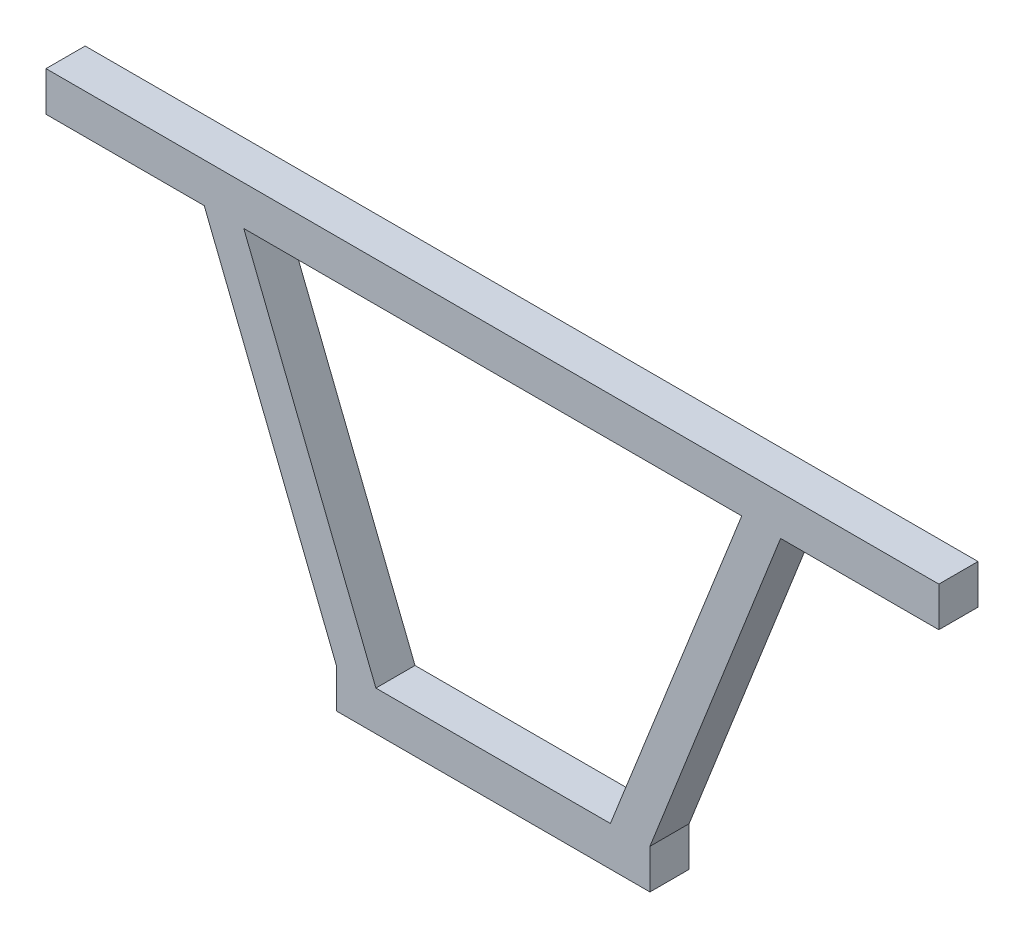
SolidWorks part; units mm, degrees
note: The reader was unsure of these and kept them because the rebuilt part matched: shared geometry of "Sketch1<3>", "Sketch1<4>".
ref_plane "Front Plane" through (0, 0, 0) normal (0, 0, 1) x (1, 0, 0)
ref_plane "Top Plane" through (0, 0, 0) normal (0, 1, 0) x (1, 0, 0)
ref_plane "Right Plane" through (0, 0, 0) normal (1, 0, 0) x (0, 0, -1)
sketch "Sketch1" plane through (0, 0, 0) normal (0, 0, 1) x (1, 0, 0)
  line L0 (0, 53.1321) -> (-114.022, 53.1321) construction
  line L1 (-114.022, 53.1321) -> (114.022, 53.1321) construction
  line L2 (114.022, 53.1321) -> (114.022, 43.0289) construction
  line L3 (114.022, 43.0289) -> (-114.022, 43.0289) construction
  line L4 (0, 53.1321) -> (0, -51.8692) construction
  line L5 (0, -51.8692) -> (40.2324, -51.8692) construction
  line L6 (40.2324, -51.8692) -> (40.2324, -41.766) construction
  line L7 (40.2324, -41.766) -> (-39.8716, -41.766) construction
  line L8 (-39.8716, -41.766) -> (-39.8716, -51.8692) construction
  line L9 (0, 43.0289) -> (-73.6091, 43.0289) construction
  line L10 (-73.6091, 43.0289) -> (73.6091, 43.0289) construction
  line L11 (73.6091, 43.0289) -> (40.2324, -41.766) construction
  line L12 (73.6091, 43.0289) -> (40.2324, -41.766)
  line L13 (-114.022, 53.1321) -> (114.022, 53.1321)
  line L14 (-114.022, 53.1321) -> (-114.022, 43.0289)
  line L15 (-114.022, 43.0289) -> (114.022, 43.0289)
  line L16 (114.022, 53.1321) -> (114.022, 43.0289)
  line L17 (-39.8716, -41.766) -> (40.2324, -41.766)
  line L18 (-39.8716, -41.766) -> (-39.8716, -51.8692)
  line L19 (-39.8716, -51.8692) -> (40.2324, -51.8692)
  line L20 (40.2324, -41.766) -> (40.2324, -51.8692)
  line L21 (-39.8716, -41.766) -> (-73.6091, 43.0289)
  line L22 (-73.6091, 43.0289) -> (-63.5059, 43.0289)
  line L23 (-63.5059, 43.0289) -> (-29.7684, -41.766)
  line L24 (-29.7684, -41.766) -> (-39.8716, -41.766)
  line L25 (40.2324, -41.766) -> (30.1292, -41.766)
  line L26 (30.1292, -41.766) -> (63.6863, 43.0289)
extrude "Extrude1" add sketch "Sketch1" along normal blind 10
extrude "Extrude2" add sketch "Sketch1<3>" along normal blind 10
sketch "Sketch1<3>" plane through (0, 0, 0) normal (0, 0, 1) x (1, 0, 0) same geometry as "Sketch1"
extrude "Extrude3" add sketch "Sketch1<4>" along normal blind 10
sketch "Sketch1<4>" plane through (0, 0, 0) normal (0, 0, 1) x (1, 0, 0) same geometry as "Sketch1"
sketch "Sketch2" plane through (0, 0, 0) normal (0, 0, 1) x (1, 0, 0)
  line L0 (-114.022, 43.0289) -> (114.022, 43.0289) construction
  line L1 (-114.022, 53.1321) -> (-104.0235, 53.1321)
  line L2 (-114.022, 53.1321) -> (-114.022, 43.0289)
  line L3 (-114.022, 43.0289) -> (-104.0235, 43.0289)
  line L4 (-104.0235, 53.1321) -> (-104.0235, 43.0289)
  line L5 (-39.8716, -51.8692) -> (40.2324, -51.8692) construction
  line L6 (-39.8716, -41.766) -> (-29.7684, -41.766)
  line L7 (-39.8716, -41.766) -> (-39.8716, -51.8692)
  line L8 (-39.8716, -51.8692) -> (-29.7684, -51.8692)
  line L9 (-29.7684, -41.766) -> (-29.7684, -51.8692)
  line L11 (40.2324, -41.766) -> (29.5889, -41.766)
  line L12 (40.2324, -41.766) -> (40.2324, -51.8692)
  line L13 (40.2324, -51.8692) -> (29.5889, -51.8692)
  line L14 (29.5889, -41.766) -> (29.5889, -51.8692)
  line L15 (114.022, 53.1321) -> (104.0235, 53.1321)
  line L16 (114.022, 53.1321) -> (114.022, 43.0289)
  line L17 (114.022, 43.0289) -> (104.0235, 43.0289)
  line L18 (104.0235, 53.1321) -> (104.0235, 43.0289)
